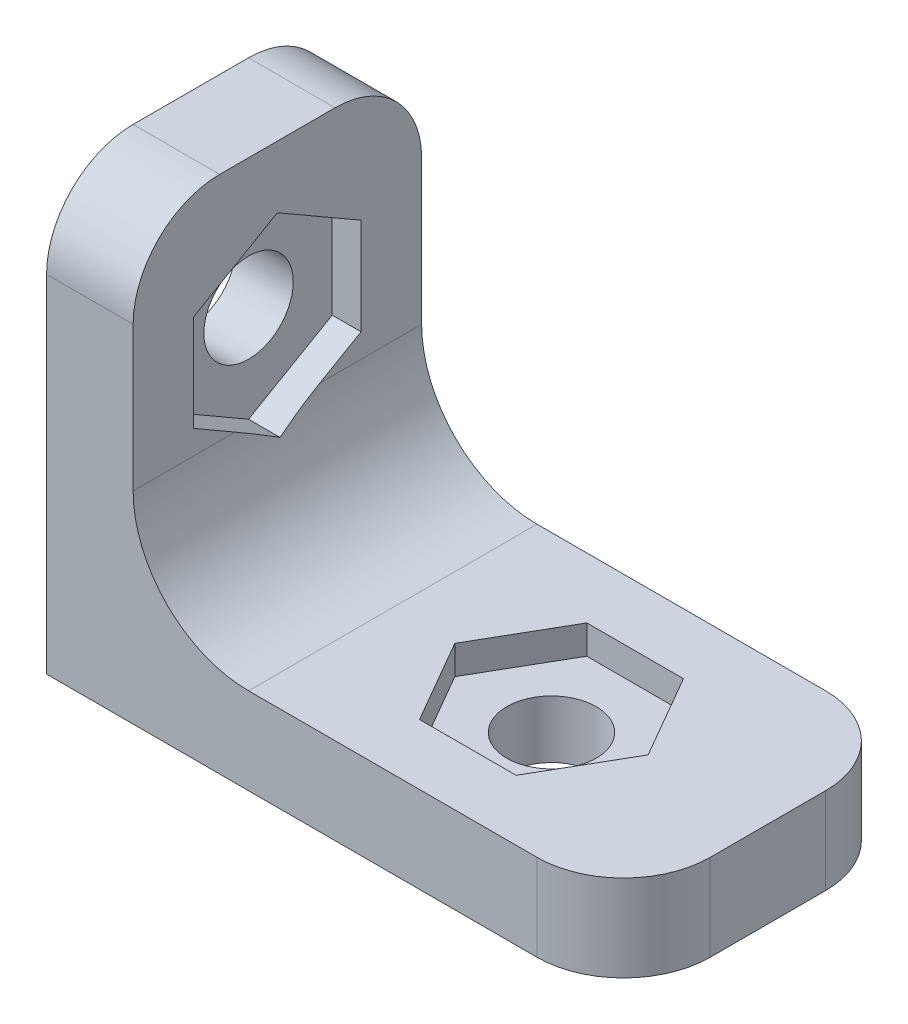
SolidWorks part; units mm, degrees
ref_plane "Alzado" through (0, 0, 0) normal (0, 0, 1) x (1, 0, 0)
ref_plane "Planta" through (0, 0, 0) normal (0, 1, 0) x (1, 0, 0)
ref_plane "Vista lateral" through (0, 0, 0) normal (1, 0, 0) x (0, 0, -1)
sketch "Croquis1" plane through (0, 0, 0) normal (0, 1, 0) x (1, 0, 0)
  line L1 (0, 0) -> (20, 0)
  line L2 (0, 0) -> (0, 10)
  line L3 (0, 10) -> (20, 10)
  line L4 (20, 0) -> (20, 10)
  circle A0 centre (12.5, 5) radius 1.55
  dimension "D3" = 3.1
  dimension "D1" = 20
  dimension "D2" = 10
  dimension "D4" = 12.5
  dimension "D5" = 5
extrude "Saliente-Extruir1" add sketch "Croquis1" along normal blind 3
sketch "Croquis2" plane through (0, 3, 0) normal (0, 1, 0) x (1, 0, 0)
  line L0 (0, 0) -> (20, 0) construction
  line L1 (0, 10) -> (3, 10)
  line L2 (0, 10) -> (0, 0)
  line L3 (0, 0) -> (3, 0)
  line L4 (3, 10) -> (3, 0)
  dimension "D1" = 3
extrude "Saliente-Extruir2" add sketch "Croquis2" along normal blind 12
sketch "Croquis3" plane through (0, 0, 0) normal (-1, 0, 0) x (0, 0, 1)
  line L0 (-10, 0) -> (0, 0) construction
  line L1 (0, 15) -> (0, 0) construction
  circle A0 centre (-5, 9.5) radius 1.55
  dimension "D1" = 3.1
  dimension "D2" = 9.5
  dimension "D3" = 5
extrude "Cortar-Extruir1" cut sketch "Croquis3" against normal up to surface (3 mm away) up to face at (3, 9, -5)
sketch "Croquis5" plane through (3, 0, 0) normal (1, 0, 0) x (0, 0, -1)
  line L1 (7.9, 11.1743) -> (5, 12.8486)
  line L2 (5, 12.8486) -> (2.1, 11.1743)
  line L3 (2.1, 11.1743) -> (2.1, 7.8257)
  line L4 (2.1, 7.8257) -> (5, 6.1514)
  line L5 (5, 6.1514) -> (7.9, 7.8257)
  line L6 (7.9, 7.8257) -> (7.9, 11.1743)
  line L8 (10, 15) -> (10, 3) construction
  circle A0 centre (5, 9.5) radius 2.9 construction
  dimension "D1" = 5.8
extrude "Cortar-Extruir3" cut sketch "Croquis5" against normal blind 1
fillet "Redondeo1" radius 3 4 edges at (1.5, 15, -10) (1.5, 15, 0) (20, 1.5, 0) (20, 1.5, -10)
fillet "Redondeo2" radius 4 1 edges at (3, 3, -5)
sketch "Croquis6" plane through (0, 3, 0) normal (0, 1, 0) x (1, 0, 0)
  line L0 (17, 10) -> (7, 10) construction
  line L1 (14.1743, 7.9) -> (10.8257, 7.9)
  line L2 (10.8257, 7.9) -> (9.1514, 5)
  line L3 (9.1514, 5) -> (10.8257, 2.1)
  line L4 (10.8257, 2.1) -> (14.1743, 2.1)
  line L5 (14.1743, 2.1) -> (15.8486, 5)
  line L6 (15.8486, 5) -> (14.1743, 7.9)
  circle A0 centre (12.5, 5) radius 2.9 construction
  dimension "D1" = 5.8
extrude "Cortar-Extruir4" cut sketch "Croquis6" against normal blind 1
